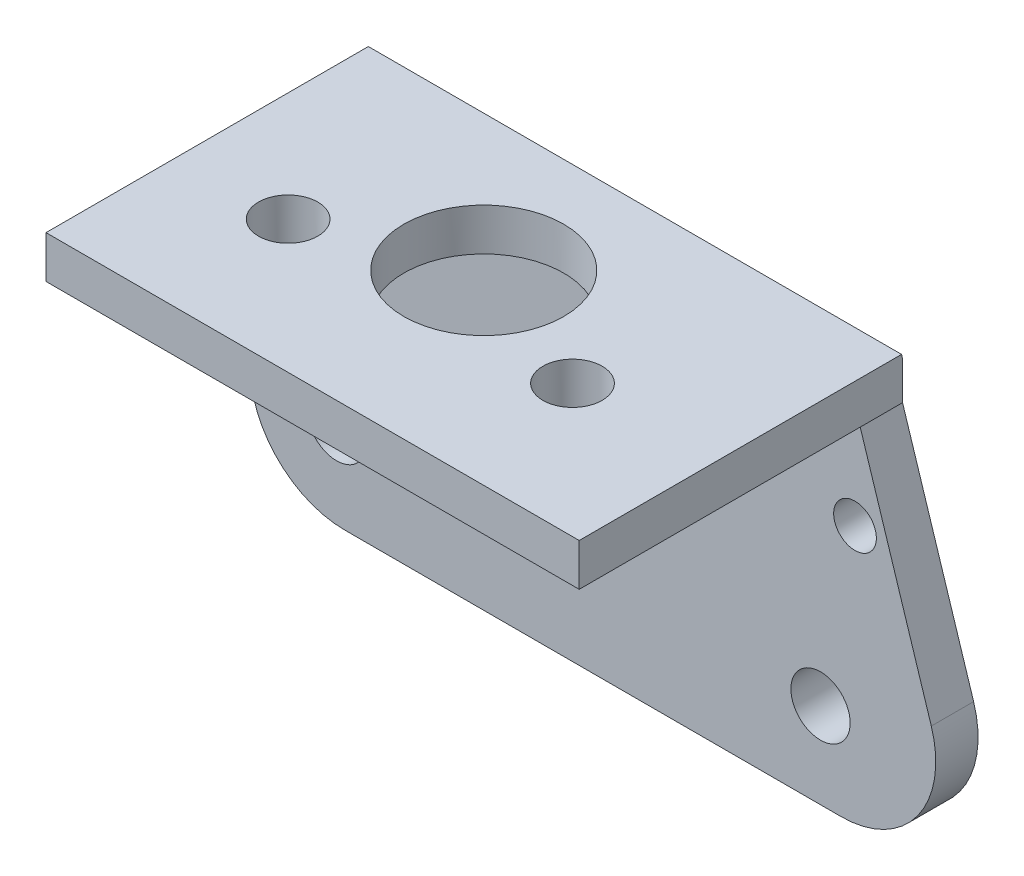
SolidWorks part; units mm, degrees
ref_plane "Front Plane" through (0, 0, 0) normal (0, 0, 1) x (1, 0, 0)
ref_plane "Top Plane" through (0, 0, 0) normal (0, 1, 0) x (1, 0, 0)
ref_plane "Right Plane" through (0, 0, 0) normal (1, 0, 0) x (0, 0, -1)
ref_plane "Plane1" through (0, 0, 5) normal (0, 0, 1) x (1, 0, 0)
sketch "Sketch1" plane through (0, 0, 5) normal (0, 0, 1) x (1, 0, 0)
  line L0 (-21.23, 0) -> (-27.3364, -18.8061)
  line L1 (-19.7275, -29.2768) -> (22.1459, -29.2768)
  line L2 (29.7692, -18.8507) -> (23.77, 0)
  line L3 (23.77, 0) -> (23.77, 5)
  line L4 (23.77, 5) -> (-21.23, 5)
  line L5 (-21.23, 5) -> (-21.23, 0)
  arc A0 (-27.3364, -18.8061) -> (-19.7275, -29.2768) centre (-19.7275, -21.2768) ccw
  arc A1 (22.1459, -29.2768) -> (29.7692, -18.8507) centre (22.1459, -21.2768) ccw
extrude "Boss-Extrude1" add sketch "Sketch1" against normal blind 3.5719
sketch "Sketch2" plane through (0, 0, 5) normal (0, 0, 1) x (1, 0, 0)
  line L0 (23.77, 0) -> (-21.23, 0)
  line L1 (-21.23, 0) -> (-21.23, 3.5719)
  line L2 (-21.23, 3.5719) -> (23.77, 3.5719)
  line L3 (23.77, 3.5719) -> (23.77, 0)
  dimension "D1" = 3.5719
extrude "Boss-Extrude2" add sketch "Sketch2" along normal blind 23.715
hole_wizard "Ø5.0 (5) Diameter Hole1" positions "Sketch4" profile "Sketch3" hole size "Ø5.0" standard "ANSI Metric"
sketch "Sketch4" plane through (0, 0, 1.4281) normal (0, 0, -1) x (-1, 0, 0)
  point P0 (-20.42, -22.057)
  point P1 (20.42, -22.057)
sketch "Sketch3" plane through (20.42, -22.057, 1.4281) normal (1, 0, 0) x (0, 1, 0)
  line L0 (0, 0) -> (0, 27.2868)
  line L1 (0, 27.2868) -> (2.5, 27.2868)
  line L2 (2.5, 27.2868) -> (2.5, 0)
  line L5 (2.5, 0) -> (0, 0)
  line L11 (0, -6.35) -> (0, 107.95) construction
  dimension "Thru Hole Dia." = 5
  dimension "Thru Hole Depth" = 27.2868
fillet "Fillet1" radius 2 1 edges at (1.27, 5, 1.4281) tangent propagation no
fillet "Fillet2" [suppressed] radius 8 tangent propagation no
hole_wizard "Ø13.5 (13.5) Diameter Hole1" positions "Sketch6" profile "Sketch5" hole size "Ø13.5" standard "ANSI Metric"
sketch "Sketch6" plane through (0, 5, 0) normal (0, 1, 0) x (1, 0, 0)
  line L0 (-55, -5) -> (55, -5) construction
  point P0 (0, -13)
  dimension "D1" = 8
sketch "Sketch5" plane through (0, 5, 13) normal (1, 0, 0) x (0, 0, 1)
  line L0 (0, 0) -> (0, 34.2768)
  line L1 (0, 34.2768) -> (6.75, 34.2768)
  line L2 (6.75, 34.2768) -> (6.75, 0)
  line L5 (6.75, 0) -> (0, 0)
  line L11 (0, -6.35) -> (0, 107.95) construction
  dimension "Thru Hole Dia." = 13.5
  dimension "Thru Hole Depth" = 34.2768
hole_wizard "Ø5.0 (5) Diameter Hole2" positions "Sketch8" profile "Sketch7" hole size "Ø5.0" standard "ANSI Metric"
sketch "Sketch8" plane through (0, 5, 0) normal (0, 1, 0) x (1, 0, 0)
  line L0 (-55, -5) -> (55, -5) construction
  point P0 (-12, -17.51)
  point P1 (12, -17.51)
  dimension "D1" = 12.51
  dimension "D2" = 12.51
  dimension "D3" = 12
  dimension "D4" = 24
sketch "Sketch7" plane through (-12, 5, 17.51) normal (1, 0, 0) x (0, 0, 1)
  line L0 (0, 0) -> (0, 34.2768)
  line L1 (0, 34.2768) -> (2.5, 34.2768)
  line L2 (2.5, 34.2768) -> (2.5, 0)
  line L5 (2.5, 0) -> (0, 0)
  line L11 (0, -6.35) -> (0, 107.95) construction
  dimension "Thru Hole Dia." = 5
  dimension "Thru Hole Depth" = 34.2768
sketch "Sketch9" plane through (0, 0, 5) normal (0, 0, 1) x (1, 0, 0)
  line L1 (-21.23, 3.5719) -> (23.77, 3.5719)
  line L2 (-21.23, 3.5719) -> (-21.23, 5)
  line L3 (-21.23, 5) -> (23.77, 5)
  line L4 (23.77, 3.5719) -> (23.77, 5)
extrude "Cut-Extrude1" cut sketch "Sketch9" against normal blind 10
sketch "Sketch10" plane through (0, 0, 5) normal (0, 0, 1) x (1, 0, 0)
  circle A0 centre (23.3301, -7.4351) radius 1.8034
  circle A1 centre (-20.8887, -7.4351) radius 1.8034
  dimension "D1" = 3.6068
  dimension "D2" = 3.6068
extrude "Cut-Extrude2" cut sketch "Sketch10" against normal through all
